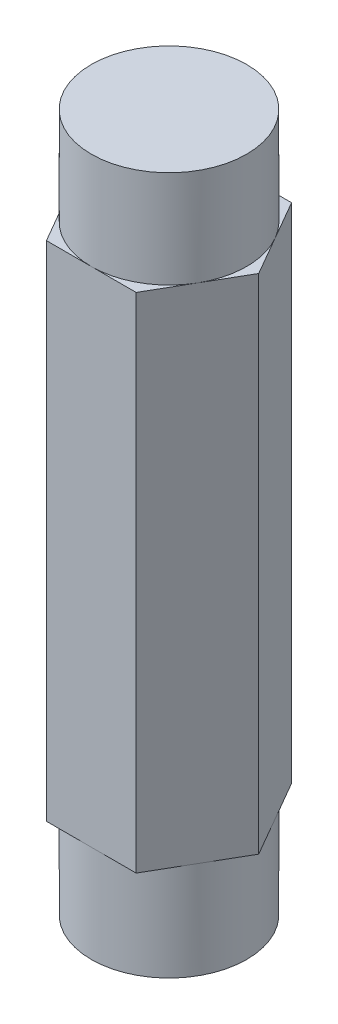
SolidWorks part; units mm, degrees
ref_plane "Front Plane" through (0, 0, 0) normal (0, 0, 1) x (1, 0, 0)
ref_plane "Top Plane" through (0, 0, 0) normal (0, 1, 0) x (1, 0, 0)
ref_plane "Right Plane" through (0, 0, 0) normal (1, 0, 0) x (0, 0, -1)
sketch "Sketch1" plane through (0, 0, 0) normal (0, 1, 0) x (1, 0, 0)
  line L1 (3.6662, -6.35) -> (7.3323, 0)
  line L2 (7.3323, 0) -> (3.6662, 6.35)
  line L3 (3.6662, 6.35) -> (-3.6662, 6.35)
  line L4 (-3.6662, 6.35) -> (-7.3323, 0)
  line L5 (-7.3323, 0) -> (-3.6662, -6.35)
  line L6 (-3.6662, -6.35) -> (3.6662, -6.35)
  circle A0 centre (0, 0) radius 6.35 construction
  dimension "D1" = 12.7
extrude "Boss-Extrude1" add sketch "Sketch1" along normal mid plane 56.9976 contours L1 L2 L3 L4 L5 L6
sketch "Sketch2" plane through (0, 28.4988, 0) normal (0, 1, 0) x (1, 0, 0)
  circle A0 centre (0, 0) radius 6.35
  dimension "D1" = 12.7
extrude "Cut-Extrude1" cut sketch "Sketch2" against normal blind 7.9502 flip side to cut
mirror "Mirror1" about plane through (0, 0, 0) normal (0, 1, 0) of "Cut-Extrude1"
